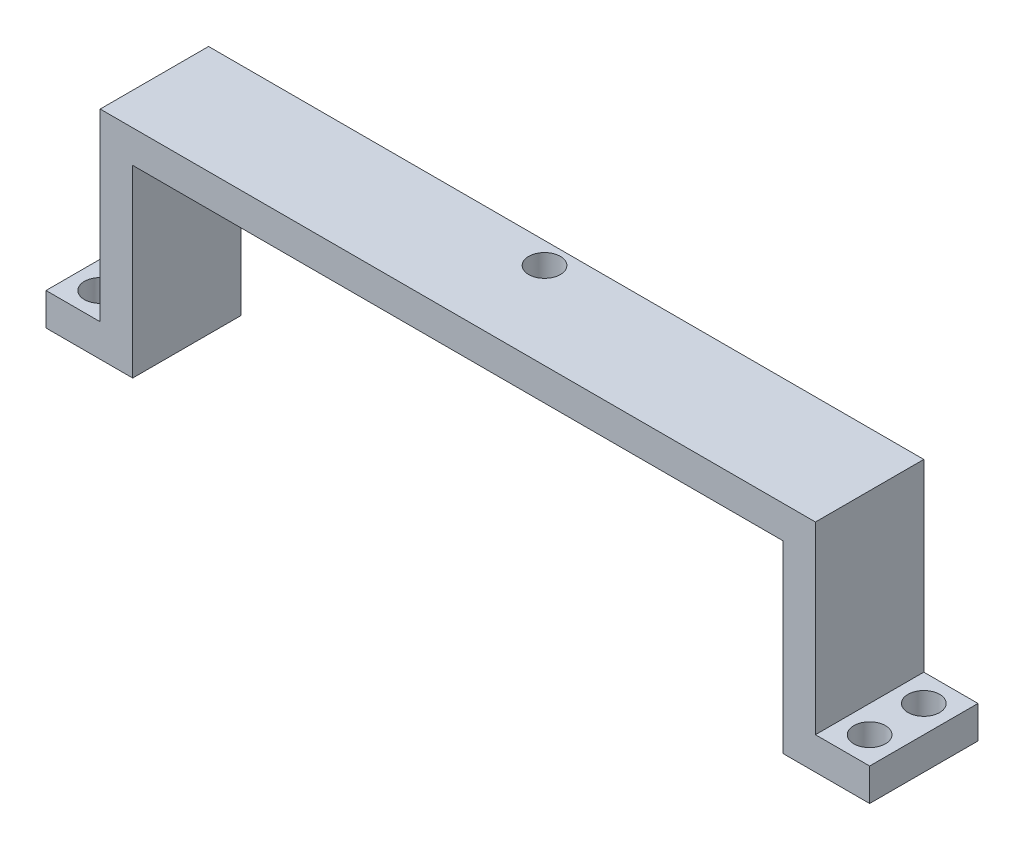
SolidWorks part; units mm, degrees
ref_plane "Front Plane" through (0, 0, 0) normal (0, 0, 1) x (1, 0, 0)
ref_plane "Top Plane" through (0, 0, 0) normal (0, 1, 0) x (1, 0, 0)
ref_plane "Right Plane" through (0, 0, 0) normal (1, 0, 0) x (0, 0, -1)
sketch "Sketch1" plane through (0, 0, 0) normal (0, 1, 0) x (1, 0, 0)
  line L0 (33, 0) -> (-33, 0)
  line L1 (-33, -5) -> (-33, 5)
  line L2 (-33, 5) -> (33, 5)
  line L3 (33, 5) -> (33, -5)
  line L4 (33, -5) -> (-33, -5)
  point P4 (0, 0)
  point P7 (-33, 0)
extrude "Boss-Extrude1" add sketch "Sketch1" along normal blind 3 contours L3 L2 L1 L0 | L4 L3 L0 L1 region at (0, 0, 2.5) region at (0, 0, -2.5)
sketch "Sketch3" plane through (0, 0, 0) normal (0, -1, 0) x (1, 0, 0)
  line L0 (-33, -5) -> (-30, -5)
  line L1 (-33, -5) -> (33, -5) construction
  line L2 (-30, -5) -> (-30, 5)
  line L3 (33, 5) -> (-33, 5) construction
  line L4 (-30, 5) -> (-33, 5)
  line L5 (-33, 5) -> (-33, -5)
  line L6 (33, -5) -> (30, -5)
  line L7 (30, -5) -> (30, 5)
  line L8 (30, 5) -> (33, 5)
  line L9 (33, -5) -> (33, 5) construction
  line L10 (33, 5) -> (33, -5)
extrude "Boss-Extrude2" add sketch "Sketch3" along normal blind 14
sketch "Sketch4" plane through (0, -14, 0) normal (0, -1, 0) x (1, 0, 0)
  line L0 (-30, -5) -> (-30, 5)
  line L1 (-30, 5) -> (-33, 5) construction
  line L2 (-30, -5) -> (-30, 5) construction
  line L3 (-30, 5) -> (-38, 5)
  line L4 (-38, 5) -> (-38, -5)
  line L5 (-38, -5) -> (-30, -5)
  line L6 (30, -5) -> (38, -5)
  line L7 (38, -5) -> (38, 5)
  line L8 (38, 5) -> (30, 5)
  line L9 (30, 5) -> (30, -5)
  line L10 (30, -5) -> (30.0498, -4.8503)
  line M1 (-33, 5) -> (-33, -5)
  line M2 (-33, -5) -> (-30, -5)
  line M3 (-30, -5) -> (-30, 5)
  line M4 (-30, 5) -> (-33, 5)
extrude "Boss-Extrude3" add sketch "Sketch4" along normal blind 3 contours L4 L5 L3 M1 | L8 L9 L6 L7 | M4 M1 M2 M3 region at (-31.5, -14, 0) region at (-35.5, -14, 0) region at (34, -14, 0)
sketch "Sketch5" plane through (0, 3, 0) normal (0, 1, 0) x (1, 0, 0)
  line L0 (-33, 5) -> (33, 5) construction
  circle A0 centre (0, 3) radius 1.46
  dimension "D1" = 2
extrude "Cut-Extrude1" cut sketch "Sketch5" against normal through all
sketch "Sketch6" plane through (0, -14, 0) normal (0, 1, 0) x (1, 0, 0)
  line L0 (-33, -5) -> (-38, -5) construction
  line L1 (-38, 5) -> (-33, 5) construction
  line L2 (-38, -5) -> (-38, 5) construction
  circle A0 centre (-35.5, -2.5) radius 1.46
  circle A1 centre (-35.5, 2.5) radius 1.46
  dimension "D1" = 2.5
  dimension "D2" = 2.5
  dimension "D3" = 2.5
  dimension "D4" = 2.5
extrude "Cut-Extrude2" cut sketch "Sketch6" against normal through all
mirror "Mirror1" about plane through (0, 0, 0) normal (1, 0, 0) of "Cut-Extrude2"
